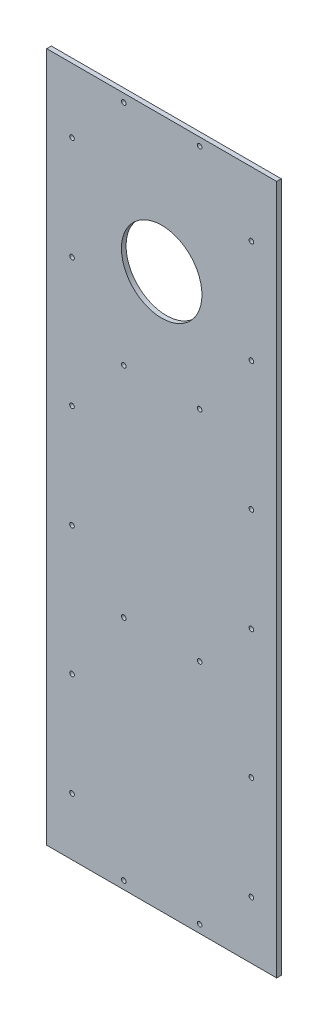
SolidWorks part; units mm, degrees
material "Alumina"
ref_plane "Front Plane" through (0, 0, 0) normal (0, 0, 1) x (1, 0, 0)
ref_plane "Top Plane" through (0, 0, 0) normal (0, 1, 0) x (1, 0, 0)
ref_plane "Right Plane" through (0, 0, 0) normal (1, 0, 0) x (0, 0, -1)
sketch "Sketch1" plane through (0, 0, 0) normal (0, 0, 1) x (1, 0, 0)
  line L1 (50, -150) -> (-50, -150)
  line L2 (50, -150) -> (50, 150)
  line L3 (50, 150) -> (-50, 150)
  line L4 (-50, -150) -> (-50, 150)
  line L5 (50, -150) -> (-50, 150) construction
  line L6 (50, 150) -> (-50, -150) construction
  point P0 (0, 0)
  dimension "D1" = 100
  dimension "D2" = 300
extrude "Boss-Extrude1" add sketch "Sketch1" along normal blind 2
sketch "Sketch2" plane through (0, 0, 2) normal (0, 0, 1) x (1, 0, 0)
  line L0 (-50, 150) -> (-50, -150) construction
  line L1 (50, 150) -> (-50, 150) construction
  line L2 (-50, -150) -> (50, -150) construction
  line L4 (0, -1.1) -> (0, 1.1) construction
  line L5 (-39, 122) -> (-39, 21) construction
  circle A0 centre (-39, 122) radius 1
  circle A1 centre (-39, 77) radius 1
  circle A2 centre (39, 122) radius 1
  circle A3 centre (39, 77) radius 1
  circle A4 centre (-39, 21) radius 1
  circle A5 centre (-39, -24) radius 1
  circle A6 centre (39, 21) radius 1
  circle A7 centre (39, -24) radius 1
  circle A8 centre (-39, -80) radius 1
  circle A9 centre (-39, -125) radius 1
  circle A10 centre (39, -80) radius 1
  circle A11 centre (39, -125) radius 1
  circle A13 centre (16.5, -146.5) radius 1
  circle A14 centre (-16.5, -146.5) radius 1
  circle A15 centre (-16.5, 146.5) radius 1
  circle A16 centre (16.5, 146.5) radius 1
  dimension "D1" = 2
  dimension "D3" = 28
  dimension "D4" = 2
  dimension "D6" = 11
  dimension "D10" = 2
  dimension "D11" = 33
  dimension "D13" = 3.5
  dimension "D14" = 78
  dimension "D15" = 11
  dimension "D5" = 3.5
  dimension "D2" = 11
  dimension "D9" = 25
  dimension "D17" = 101
  dimension "D7" = 2
  dimension "D8" = 3
  dimension "D12" = 2
extrude "Cut-Extrude1" cut sketch "Sketch2" against normal blind 10
sketch "Sketch3" plane through (0, 0, 0) normal (0, 0, -1) x (-1, 0, 0)
  line L0 (-50, 150) -> (50, 150) construction
  line L1 (-50, -150) -> (-50, 150) construction
  circle A0 centre (0, 91) radius 17.5
  dimension "D2" = 35
  dimension "D3" = 50
  dimension "D1" = 59
extrude "Cut-Extrude2" cut sketch "Sketch3" against normal blind 10
sketch "Sketch5" plane through (0, 0, 2) normal (0, 0, 1) x (1, 0, 0)
  line L0 (-16.5, 47.5) -> (-16.5, -47.5) construction
  line L1 (-16.5, -47.5) -> (16.5, -47.5) construction
  line L2 (16.5, -47.5) -> (16.5, 47.5) construction
  line L3 (16.5, 47.5) -> (-16.5, 47.5) construction
  line L4 (-16.5, 146.5) -> (-16.5, 47.5) construction
  line L5 (16.5, 146.5) -> (16.5, 47.5) construction
  circle A6 centre (-16.5, 47.5) radius 1
  circle A7 centre (16.5, 47.5) radius 1
  circle A8 centre (-16.5, -47.5) radius 1
  circle A9 centre (16.5, -47.5) radius 1
  circle A10 centre (-16.5, 146.5) radius 1 construction
  circle A11 centre (16.5, 146.5) radius 1 construction
  point P5 (16.5426, 146.5)
  point P6 (-16.615, 146.5)
  dimension "D1" = 99
  dimension "D3" = 2
  dimension "D4" = 2
  dimension "D5" = 2
  dimension "D6" = 2
  dimension "D2" = 95
extrude "Cut-Extrude3" cut sketch "Sketch5" against normal blind 10
